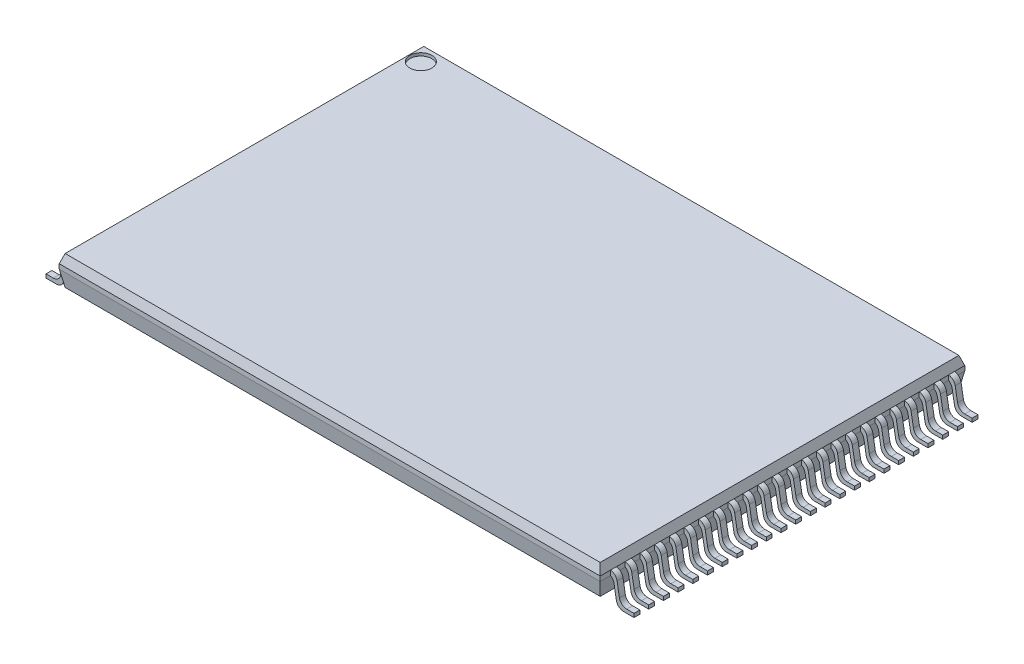
SolidWorks part; units mm, degrees
ref_plane "Front Plane" through (0, 0, 0) normal (0, 0, 1) x (1, 0, 0)
ref_plane "Top Plane" through (0, 0, 0) normal (0, 1, 0) x (1, 0, 0)
ref_plane "Right Plane" through (0, 0, 0) normal (1, 0, 0) x (0, 0, -1)
sketch "Sketch1" plane through (0, 0, 0) normal (0, 0, 1) x (1, 0, 0)
  line L0 (-0.3349, 0.1332) -> (-0.4164, -0.3286)
  line L1 (-0.016, 0.4648) -> (-0.1936, 0.4648)
  line L2 (-0.016, 0.4648) -> (-0.016, 0.3398)
  line L3 (-0.6626, -0.5352) -> (-1.016, -0.5352)
  line L4 (-1.016, -0.4102) -> (-1.016, -0.5352)
  line L5 (-1.016, -0.5352) -> (-0.496, -0.5352)
  line L6 (-1.016, -0.5352) -> (-1.016, -0.4102)
  line L7 (-1.016, -0.4102) -> (-0.7675, -0.4102)
  line L9 (-0.016, 0.4648) -> (-0.266, 0.4648)
  line L10 (-0.016, 0.4648) -> (-0.016, 0.3398)
  line L11 (-0.016, 0.3398) -> (-0.0887, 0.3398)
  line L13 (-0.4398, 0.2582) -> (-0.5213, -0.2036)
  arc A0 (-0.3349, 0.1332) -> (-0.0887, 0.3398) centre (-0.0887, 0.0898) cw
  arc A1 (-0.4398, 0.2582) -> (-0.1936, 0.4648) centre (-0.1936, 0.2148) cw
  arc A2 (-0.7675, -0.4102) -> (-0.5213, -0.2036) centre (-0.7675, -0.1602) ccw
  arc A3 (-0.6626, -0.5352) -> (-0.4164, -0.3286) centre (-0.6626, -0.2852) ccw
  dimension "D3" = 0.25
  dimension "D1" = 1
  dimension "D2" = 1
  dimension "D4" = 0.125
  dimension "D6" = 0.125
  dimension "D7" = 80
  dimension "D8" = 0.125
extrude "Boss-Extrude1" add sketch "Sketch1" along normal blind 0.2 contours L3 A3 L0 A0 L11 L2 L1 A1 L13 A2 L7 L4 region at (-0.4788, -0.0796, 0)
pattern_linear "LPattern1" count 24 spacing 0.5 along (0, 0, 1) of bodies 101
ref_plane "Plane2" through (8.984, 0, 0) normal (-1, 0, 0) x (0, 0, 1)
mirror "Mirror1" about plane through (8.984, 0, 0) normal (-1, 0, 0) of bodies 101 102 103 104 105 106 107 109 108 110 111 112 113 114 115 116 117 118 119 120 121 122 123 124
sketch "Sketch2" plane through (0, 0.4648, 0) normal (0, 1, 0) x (1, 0, 0)
  line L0 (17.984, -0.2) -> (17.984, 0) construction
  line L1 (-0.216, 0.35) -> (18.184, 0.35)
  line L2 (-0.216, 0.35) -> (-0.216, -12.05)
  line L3 (-0.216, -12.05) -> (18.184, -12.05)
  line L4 (18.184, 0.35) -> (18.184, -12.05)
  line L5 (-0.016, 0) -> (-0.1936, 0) construction
  point P6 (-0.1048, 0)
  dimension "D1" = 18.4
  dimension "D2" = 12.4
  dimension "D3" = 0.2
  dimension "D4" = 0.35
extrude "Boss-Extrude2" add sketch "Sketch2" against normal blind 0.7 contours L1 L4 L3 L2
sketch "Sketch4" plane through (0, 0.4648, 0) normal (0, 1, 0) x (1, 0, 0)
  line L1 (-0.216, 0.35) -> (18.184, 0.35)
  line L2 (-0.216, 0.35) -> (-0.216, -12.05)
  line L3 (-0.216, -12.05) -> (18.184, -12.05)
  line L4 (18.184, 0.35) -> (18.184, -12.05)
extrude "Boss-Extrude3" add sketch "Sketch4" along normal blind 0.3
sketch "Sketch5" plane through (0, 0, 12.05) normal (0, 0, 1) x (1, 0, 0)
  line L0 (18.184, 0.7648) -> (18.184, 0.4638)
  line L1 (18.184, 0.4638) -> (18.084, 0.7648)
  line L2 (18.184, 0.7648) -> (-0.216, 0.7648) construction
  line L3 (18.084, 0.7648) -> (18.184, 0.7648)
  line L4 (18.184, 0.305) -> (18.184, -0.2352)
  line L5 (18.184, -0.2352) -> (18.084, -0.2352)
  line L6 (-0.216, -0.2352) -> (18.184, -0.2352) construction
  line L7 (18.084, -0.2352) -> (18.184, 0.305)
  line L8 (-0.216, 0.4638) -> (-0.216, 0.7648)
  line L9 (-0.216, 0.7648) -> (-0.116, 0.7648)
  line L10 (-0.116, 0.7648) -> (-0.216, 0.4638)
  line L11 (-0.216, 0.305) -> (-0.216, -0.2352)
  line L12 (-0.216, -0.2352) -> (-0.116, -0.2352)
  line L13 (-0.116, -0.2352) -> (-0.216, 0.305)
  dimension "D1" = 0.1
  dimension "D2" = 0.1
  dimension "D3" = 0.1
  dimension "D4" = 0.1
extrude "Cut-Extrude1" cut sketch "Sketch5" against normal through all
sketch "Sketch6" plane through (-0.216, 0, 0) normal (-1, 0, 0) x (0, 0, 1)
  line L0 (-0.35, 0.4638) -> (-0.35, 0.7648)
  line L1 (-0.35, 0.7648) -> (-0.25, 0.7648)
  line L2 (-0.35, 0.7648) -> (12.05, 0.7648) construction
  line L3 (-0.25, 0.7648) -> (-0.35, 0.4638)
  line L4 (-0.35, 0.305) -> (-0.35, -0.2352)
  line L5 (-0.35, -0.2352) -> (-0.25, -0.2352)
  line L6 (-0.35, -0.2352) -> (12.05, -0.2352) construction
  line L7 (-0.25, -0.2352) -> (-0.35, 0.305)
  line L8 (12.05, 0.4638) -> (12.05, 0.7648)
  line L9 (12.05, 0.7648) -> (11.95, 0.7648)
  line L10 (11.95, 0.7648) -> (12.05, 0.4638)
  line L11 (12.05, -0.2352) -> (12.05, 0.305)
  line L12 (12.05, 0.305) -> (11.95, -0.2352)
  line L13 (11.95, -0.2352) -> (12.05, -0.2352)
  dimension "D1" = 0.1
  dimension "D2" = 0.1
  dimension "D3" = 0.1
  dimension "D4" = 0.1
extrude "Cut-Extrude2" cut sketch "Sketch6" against normal through all
sketch "Sketch7" plane through (0, 0.7648, 0) normal (0, 1, 0) x (1, 0, 0)
  line L0 (18.084, 0.25) -> (-0.116, 0.25) construction
  line L1 (-0.116, 0.25) -> (-0.116, -11.95) construction
  circle A0 centre (0.284, -0.25) radius 0.375
  dimension "D1" = 0.75
  dimension "D2" = 0.5
  dimension "D3" = 0.4
extrude "Cut-Extrude4" cut sketch "Sketch7" against normal blind 0.1
